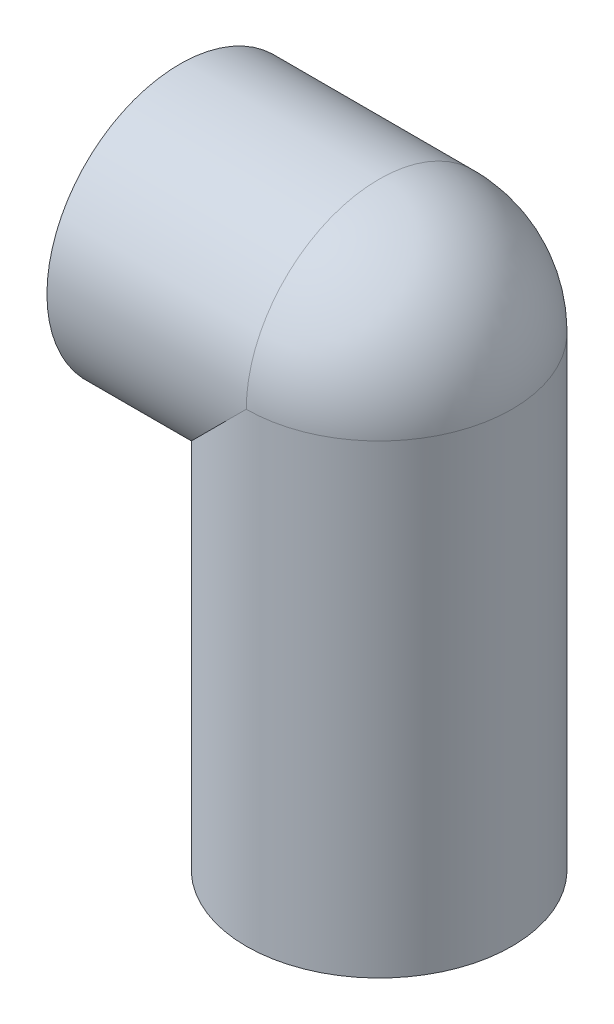
SolidWorks part; units mm, degrees
ref_plane "Front Plane" through (0, 0, 0) normal (0, 0, 1) x (1, 0, 0)
ref_plane "Top Plane" through (0, 0, 0) normal (0, 1, 0) x (1, 0, 0)
ref_plane "Right Plane" through (0, 0, 0) normal (1, 0, 0) x (0, 0, -1)
sketch "Sketch1" plane through (0, 110, 0) normal (0, 1, 0) x (1, 0, 0)
  line L0 (60, 20) -> (60, -20)
  arc A0 (60, -20) -> (60, 20) centre (60, 0) ccw
extrude "Boss-Extrude1" add sketch "Sketch1" along normal blind 90
fillet "Fillet1" radius 20 1 edges at (80, 200, 0) conic radius 20
sketch "Sketch3" plane through (60, 0, 0) normal (-1, 0, 0) x (0, 0, 1)
  circle A0 centre (0, 180) radius 20
extrude "Boss-Extrude2" add sketch "Sketch3" along normal blind 30
sketch "Sketch4" plane through (0, 110, 0) normal (0, 1, 0) x (1, 0, 0)
  line L0 (60, 20) -> (60, -20) construction
  line L1 (60, 20) -> (60, -20)
  arc A0 (60, 20) -> (60, -20) centre (60, 0) ccw
extrude "Boss-Extrude3" add sketch "Sketch4" along normal blind 70
